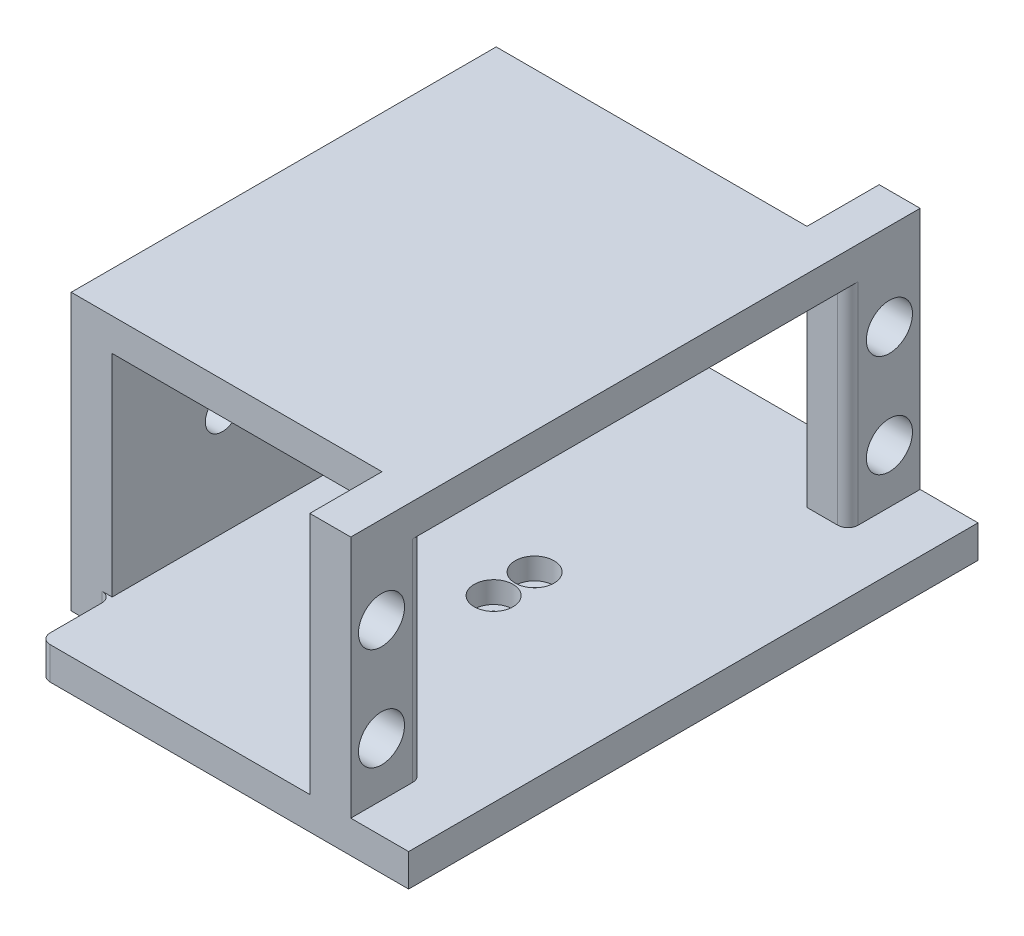
SolidWorks part; units mm, degrees
ref_plane "Front Plane" through (0, 0, 0) normal (0, 0, 1) x (1, 0, 0)
ref_plane "Top Plane" through (0, 0, 0) normal (0, 1, 0) x (1, 0, 0)
ref_plane "Right Plane" through (0, 0, 0) normal (1, 0, 0) x (0, 0, -1)
sketch "Sketch1" plane through (0, 0, 0) normal (0, 1, 0) x (1, 0, 0)
  line L1 (-20, 27.8) -> (20, 27.8)
  line L2 (-20, 27.8) -> (-20, -27.8)
  line L3 (-20, -27.8) -> (20, -27.8)
  line L4 (20, 27.8) -> (20, -27.8)
  line L5 (-20, 27.8) -> (20, -27.8) construction
  line L6 (-20, -27.8) -> (20, 27.8) construction
  point P0 (0, 0)
  dimension "D1" = 55.6
  dimension "D2" = 40
extrude "Boss-Extrude1" add sketch "Sketch1" along normal blind 3.175
sketch "Sketch2" plane through (0, 3.175, 0) normal (0, 1, 0) x (1, 0, 0)
  line L0 (-20, 27.8) -> (-20, -27.8) construction
  line L1 (-16, 20.75) -> (-20, 20.75)
  line L2 (-16, 20.75) -> (-16, -20.75)
  line L3 (-16, -20.75) -> (-20, -20.75)
  line L4 (-20, 20.75) -> (-20, -20.75)
  line L5 (-16, 20.75) -> (-20, -20.75) construction
  line L6 (-16, -20.75) -> (-20, 20.75) construction
  line L8 (-20, -27.8) -> (20, -27.8) construction
  line L9 (-20, 0) -> (65.8452, 0) construction
  line L12 (10.35, 27.8) -> (10.35, 20.75)
  line L13 (14.35, -27.8) -> (10.35, -27.8)
  line L14 (14.35, -27.8) -> (14.35, -20.75)
  line L15 (14.35, -20.75) -> (10.35, -20.75)
  line L16 (10.35, -27.8) -> (10.35, -20.75)
  line L17 (14.35, 20.75) -> (10.35, 20.75)
  line L18 (14.35, 27.8) -> (14.35, 20.75)
  line L19 (14.35, 27.8) -> (10.35, 27.8)
  line L27 (-5.55, 20.1) -> (14.25, 20.1) construction
  line L28 (-5.55, -20.1) -> (14.25, -20.1) construction
  line L30 (20, -27.8) -> (20, 27.8) construction
  point P0 (-18, 0)
  dimension "D1" = 4
  dimension "D4" = 4
  dimension "D6" = 7.05
  dimension "D9" = 41.5
  dimension "D2" = 41.5
  dimension "D3" = 0.65
  dimension "D7" = 0.65
  dimension "D5" = 5.65
extrude "Boss-Extrude2" add sketch "Sketch2" along normal blind 20.6
sketch "Sketch3" plane through (0, 23.775, 0) normal (0, 1, 0) x (1, 0, 0)
  line L0 (-20, 20.75) -> (10.35, 20.75)
  line L16 (14.35, -27.8) -> (10.35, -27.8)
  line L17 (10.35, -27.8) -> (10.35, -20.75)
  line L18 (10.35, -20.75) -> (-20, -20.75)
  line L19 (-20, -20.75) -> (-20, 20.75)
  line L20 (10.35, 20.75) -> (10.35, 27.8)
  line L21 (10.35, 27.8) -> (14.35, 27.8)
  line L22 (14.35, 27.8) -> (14.35, -27.8)
extrude "Boss-Extrude3" add sketch "Sketch3" along normal blind 3.175
sketch "Sketch5" plane through (14.35, 0, 0) normal (1, 0, 0) x (0, 0, -1)
  line L0 (-27.8, 26.95) -> (-27.8, 3.175) construction
  line L1 (-27.8, 3.175) -> (-20.75, 3.175) construction
  line L2 (0, 0) -> (0, 26.95) construction
  line L3 (-27.8, 26.95) -> (27.8, 26.95) construction
  circle A0 centre (-24.8, 8.425) radius 2.25
  circle A1 centre (-24.8, 18.425) radius 2.25
  circle A2 centre (24.8, 18.425) radius 2.25
  circle A3 centre (24.8, 8.425) radius 2.25
  dimension "D1" = 4.5
  dimension "D3" = 5.25
  dimension "D2" = 3
  dimension "D4" = 10
extrude "Cut-Extrude2" cut sketch "Sketch5" against normal up to surface (4 mm away) up to face at (10.35, 16.805, 23.57)
sketch "Sketch6" plane through (-20, 0, 0) normal (-1, 0, 0) x (0, 0, 1)
  circle A0 centre (10, 13.43) radius 1.65
  dimension "D1" = 3.3
extrude "Cut-Extrude3" cut sketch "Sketch6" against normal up to surface (4 mm away) contours A0 up to face at (-16, 13.475, 0)
fillet "Fillet1" radius 1 2 edges at (14.35, 13.475, 20.75) (14.35, 13.475, -20.75)
sketch "Sketch7" plane through (0, 3.175, 0) normal (0, 1, 0) x (1, 0, 0)
  line L1 (-20, -27.8) -> (-16, -27.8)
  line L2 (-20, -27.8) -> (-20, -20.75)
  line L3 (-20, -20.75) -> (-16, -20.75)
  line L4 (-16, -27.8) -> (-16, -20.75)
  line L5 (-20, 27.8) -> (-16, 27.8)
  line L6 (-20, 27.8) -> (-20, 20.75)
  line L7 (-20, 20.75) -> (-16, 20.75)
  line L8 (-16, 27.8) -> (-16, 20.75)
extrude "Cut-Extrude4" cut sketch "Sketch7" against normal up to surface (3.175 mm away) up to face at (0, 0, 0)
fillet "Fillet2" radius 1 4 edges at (-16, 1.5875, 27.8) (-16, 1.5875, 20.75) (-16, 1.5875, -20.75) (-16, 1.5875, -27.8)
sketch "Sketch8" plane through (0, 0, 0) normal (0, -1, 0) x (1, 0, 0)
  line L0 (-20, 0) -> (20, 0) construction
  line L1 (-20, -20.75) -> (-20, 20.75) construction
  line L2 (20, 27.8) -> (20, -27.8) construction
  line L3 (2.5, 27.8) -> (2.5, -27.8) construction
  line L5 (-15, 27.8) -> (20, 27.8) construction
  line L6 (20, -27.8) -> (-15, -27.8) construction
  circle A0 centre (2.5, 0) radius 4 construction
  circle A1 centre (2.5, -2) radius 1.1
  circle A2 centre (2.5, 2) radius 1.1
  dimension "D1" = 8
  dimension "D2" = 2.2
  dimension "D3" = 2
  dimension "D4" = 2
extrude "Cut-Extrude6" cut sketch "Sketch8" against normal up to surface (3.175 mm away) up to face at (0.2688, 3.175, 0)
sketch "Sketch9" plane through (0, 3.175, 0) normal (0, 1, 0) x (1, 0, 0)
  circle A0 centre (2.5, -2) radius 1.9
  circle A1 centre (2.5, 2) radius 1.9
  dimension "D1" = 3.8
extrude "Cut-Extrude7" cut sketch "Sketch9" against normal blind 2.1
equation "\"D4@Sketch2\"=\"D1@Sketch2\""
equation "\"D2@Sketch2\"=\"D9@Sketch2\""
